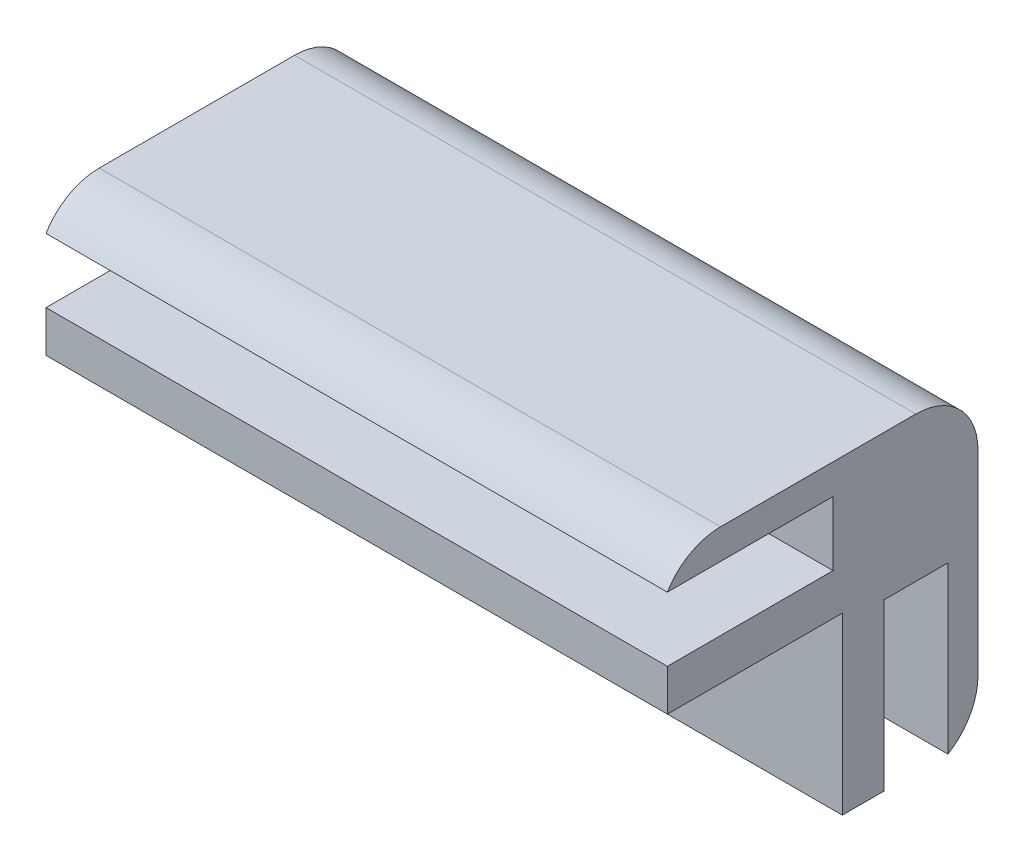
SolidWorks part; units mm, degrees
ref_plane "Front Plane" through (0, 0, 0) normal (0, 0, 1) x (1, 0, 0)
ref_plane "Top Plane" through (0, 0, 0) normal (0, 1, 0) x (1, 0, 0)
ref_plane "Right Plane" through (0, 0, 0) normal (1, 0, 0) x (0, 0, -1)
sketch "Sketch1" plane through (0, 0, 0) normal (0, 1, 0) x (1, 0, 0)
  line L1 (-34.2361, 7.7778) -> (-4.2361, 7.7778)
  line L2 (-34.2361, 7.7778) -> (-34.2361, -7.2222)
  line L3 (-34.2361, -7.2222) -> (-4.2361, -7.2222)
  line L4 (-4.2361, 7.7778) -> (-4.2361, -7.2222)
  line L5 (-34.2361, 7.7778) -> (-4.2361, -7.2222) construction
  line L6 (-34.2361, -7.2222) -> (-4.2361, 7.7778) construction
  point P0 (-19.2361, 0.2778)
  dimension "D1" = 30
  dimension "D2" = 15
extrude "Boss-Extrude1" add sketch "Sketch1" along normal blind 15
ref_plane "Plane1" through (0, 0, -4.7778) normal (0, 0, -1) x (-1, 0, 0)
sketch "Sketch2" plane through (0, 0, -4.7778) normal (0, 0, -1) x (-1, 0, 0)
  line L0 (4.2361, 15) -> (4.2361, 0) construction
  line L3 (4.2361, 8) -> (34.2361, 8)
  line L4 (4.2361, 8) -> (4.2361, 0)
  line L5 (4.2361, 0) -> (34.2361, 0)
  line L6 (34.2361, 8) -> (34.2361, 0)
  line L7 (4.2361, 15) -> (34.2361, 15) construction
  dimension "D1" = 7
extrude "Cut-Extrude1" cut sketch "Sketch2" against normal blind 1.55 and the other way blind 1.55
ref_plane "Plane4" through (0, 12, 0) normal (0, 1, 0) x (1, 0, 0)
sketch "Sketch4" plane through (0, 12, 0) normal (0, 1, 0) x (1, 0, 0)
  line L0 (-4.2361, -7.2222) -> (-4.2361, 3.2278) construction
  line L1 (-34.2361, -7.2222) -> (-4.2361, -7.2222)
  line L2 (-34.2361, -7.2222) -> (-34.2361, 0.7778)
  line L3 (-34.2361, 0.7778) -> (-4.2361, 0.7778)
  line L4 (-4.2361, -7.2222) -> (-4.2361, 0.7778)
  line L5 (-4.2361, 7.7778) -> (-34.2361, 7.7778) construction
  dimension "D1" = 7
extrude "Cut-Extrude2" cut sketch "Sketch4" against normal blind 1.55 and the other way blind 1.55
sketch "Sketch5" plane through (-34.2361, 0, 0) normal (-1, 0, 0) x (0, 0, 1)
  line L0 (-0.7778, 10.45) -> (7.2222, 10.45) construction
  line L1 (7.2222, 0) -> (-1.2278, 0)
  line L2 (7.2222, 0) -> (7.2222, 8.45)
  line L3 (7.2222, 8.45) -> (-1.2278, 8.45)
  line L4 (-1.2278, 0) -> (-1.2278, 8.45)
  line L5 (-3.2278, 0) -> (-3.2278, 8) construction
  dimension "D1" = 2
  dimension "D2" = 2
extrude "Cut-Extrude3" cut sketch "Sketch5" against normal through all
fillet "Fillet1" radius 3 3 edges at (-19.2361, 15, 7.2222) (-19.2361, 15, -7.7778) (-19.2361, 0, -7.7778)
